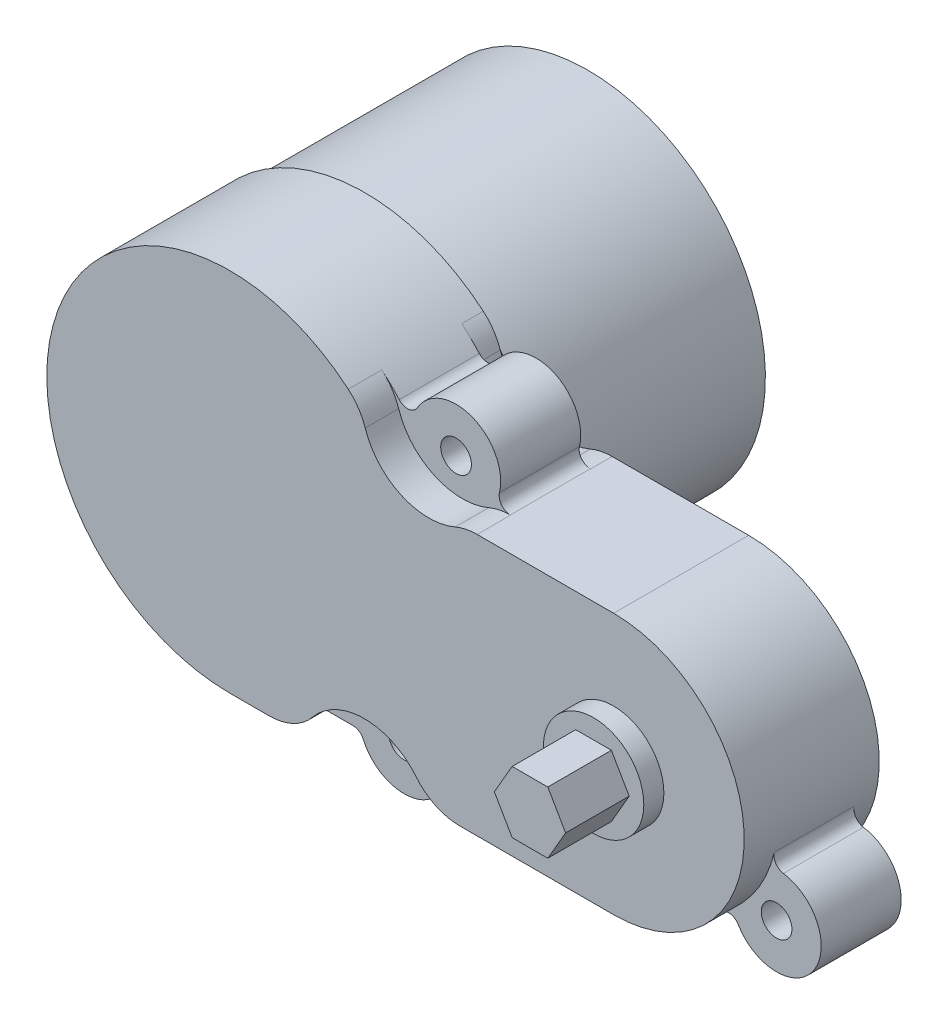
SolidWorks part; units mm, degrees
ref_plane "Front Plane" through (0, 0, 0) normal (0, 0, 1) x (1, 0, 0)
ref_plane "Top Plane" through (0, 0, 0) normal (0, 1, 0) x (1, 0, 0)
ref_plane "Right Plane" through (0, 0, 0) normal (1, 0, 0) x (0, 0, -1)
sketch "Sketch1" plane through (0, 0, 0) normal (0, 0, 1) x (1, 0, 0)
  line L0 (0, -16.4) -> (34.4, -16.4)
  line L1 (34.4, 7) -> (14.831, 7)
  arc A0 (14.831, 7) -> (0, -16.4) centre (0, 0) ccw
  arc A1 (34.4, -16.4) -> (34.4, 7) centre (34.4, -4.7) ccw
  dimension "D1" = 32.8
  dimension "D2" = 23.4
  dimension "D3" = 62.5
extrude "Boss-Extrude1" add sketch "Sketch1" along normal blind 12.1
ref_plane "Plane1" through (0, 0, 9.1) normal (0, 0, 1) x (1, 0, 0)
sketch "Sketch2" plane through (0, 0, 9.1) normal (0, 0, 1) x (1, 0, 0)
  line L0 (0, -16.4) -> (34.4, -16.4) construction
  circle A0 centre (17.2763, 9.163) radius 4
  circle A1 centre (46, -12.5384) radius 4
  circle A2 centre (12.6224, -15.4) radius 4
  arc A3 (34.4, -16.4) -> (34.4, 7) centre (34.4, -4.7) ccw construction
  arc A4 (14.831, 7) -> (0, -16.4) centre (0, 0) ccw construction
  point P6 (51.8813, -14.2344)
  point P10 (16.6547, 8.304)
  point P11 (14.1182, -17.2349)
  point P12 (16.4386, 8.0039)
  point P13 (16.493, 8.0805)
  point P16 (43.9527, -14.9346)
  dimension "D1" = 8
  dimension "D5" = 14
  dimension "D6" = 3
  dimension "D7" = 66.4
  dimension "D2" = 25
  dimension "D3" = 33.5
  dimension "D4" = 36
extrude "Boss-Extrude2" add sketch "Sketch2" against normal blind 7.17
sketch "Sketch3" plane through (0, 0, 0) normal (0, 0, -1) x (-1, 0, 0)
  circle A0 centre (0, 0) radius 15.9
  dimension "D1" = 31.8
extrude "Boss-Extrude3" add sketch "Sketch3" along normal blind 20
sketch "Sketch4" plane through (0, 0, -20) normal (0, 0, -1) x (-1, 0, 0)
  circle A0 centre (0, 0) radius 3.75
  dimension "D1" = 7.5
extrude "Boss-Extrude4" add sketch "Sketch4" along normal blind 3.2
sketch "Sketch5" plane through (0, 0, 12.1) normal (0, 0, 1) x (1, 0, 0)
  circle A0 centre (34.4, -4.7) radius 4.5
  dimension "D1" = 9
extrude "Boss-Extrude5" add sketch "Sketch5" along normal blind 1.8
sketch "Sketch6" plane through (0, 0, 13.9) normal (0, 0, 1) x (1, 0, 0)
  line L1 (35.9964, -7.465) -> (37.5927, -4.7)
  line L2 (37.5927, -4.7) -> (35.9964, -1.935)
  line L3 (35.9964, -1.935) -> (32.8036, -1.935)
  line L4 (32.8036, -1.935) -> (31.2073, -4.7)
  line L5 (31.2073, -4.7) -> (32.8036, -7.465)
  line L6 (32.8036, -7.465) -> (35.9964, -7.465)
  circle A0 centre (34.4, -4.7) radius 2.765 construction
  dimension "D1" = 5.53
extrude "Boss-Extrude6" add sketch "Sketch6" along normal offset from surface (5.7 mm away) 7.5 up to face at (38.9, -4.7, 12.1) offset beyond the face yes
sketch "Sketch8" plane through (0, 0, 12.1) normal (0, 0, 1) x (1, 0, 0)
  line L0 (17.2763, 9.163) -> (16.7178, 6.2154) construction
  line L1 (17.2763, 9.163) -> (17.8348, 12.1106) construction
  line L2 (12.6224, -15.4) -> (13.1809, -12.4524) construction
  line L3 (12.064, -18.3476) -> (12.6224, -15.4) construction
  circle A0 centre (17.8348, 12.1106) radius 6
  circle A1 centre (12.064, -18.3476) radius 6
  point P6 (17.2763, 9.163)
  point P7 (17.8348, 12.1106)
  point P8 (12.6224, -15.4)
  dimension "D1" = 3
  dimension "D2" = 12
extrude "Cut-Extrude2" cut sketch "Sketch8" against normal up to surface (3 mm away) up to face at (16.8236, 9.4224, 9.1)
sketch "Sketch7" plane through (0, 0, 9.1) normal (0, 0, 1) x (1, 0, 0)
  circle A0 centre (17.2763, 9.163) radius 1.375
  circle A1 centre (46, -12.5384) radius 1.375
  circle A2 centre (12.6224, -15.4) radius 1.375
  dimension "D1" = 2.75
extrude "Cut-Extrude1" cut sketch "Sketch7" against normal through all
sketch "Sketch9" plane through (0, 0, 0) normal (0, 0, -1) x (-1, 0, 0)
  circle A0 centre (-12.064, -18.3476) radius 6 construction
  circle A1 centre (-17.8348, 12.1106) radius 6 construction
  circle A2 centre (-12.064, -18.3476) radius 6
  circle A3 centre (-17.8348, 12.1106) radius 6
extrude "Cut-Extrude3" cut sketch "Sketch9" against normal up to surface (1.93 mm away) up to face at (18.6513, 9.163, 1.93)
fillet "Fillet1" radius 1 6 edges at (8.7495, -16.4, 5.515) (16.4954, -16.4, 5.515) (42.1161, -13.495, 5.515) (45.4386, -8.578, 5.515) (13.2998, 9.5956, 5.515) (20.641, 7, 5.515)
fillet "Fillet2" radius 5 8 edges at (6.3889, -16.4, 0.965) (17.7391, -16.4, 0.965) (6.3889, -16.4, 10.6) (17.7391, -16.4, 10.6) (11.8905, 11.295, 0.965) (21.4232, 7.3019, 0.965) (21.4232, 7.3019, 10.6) (11.8905, 11.295, 10.6)
ref_plane "Plane for mirroring part" through (-23, 0, 0) normal (1, 0, 0) x (0, 0, -1)
